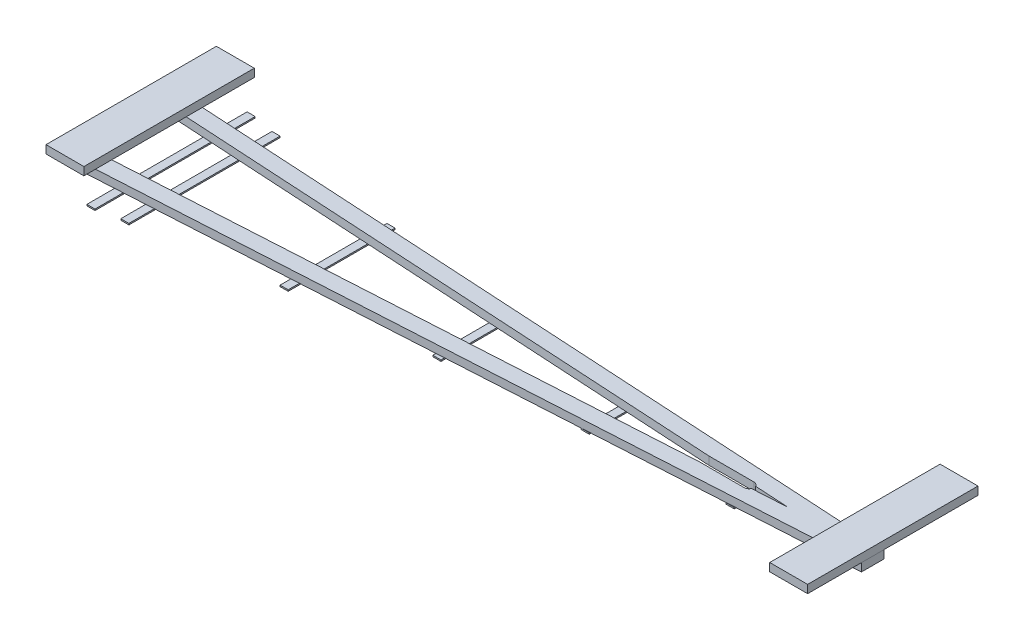
SolidWorks part; units mm, degrees
ref_plane "Front Plane" through (0, 0, 0) normal (0, 0, 1) x (1, 0, 0)
ref_plane "Top Plane" through (0, 0, 0) normal (0, 1, 0) x (1, 0, 0)
ref_plane "Right Plane" through (0, 0, 0) normal (1, 0, 0) x (0, 0, -1)
sketch "Sketch2" plane through (0, 0, 0) normal (0, 1, 0) x (1, 0, 0)
  line L0 (23, 0) -> (23, 355.0006)
  line L1 (23, 355.0006) -> (42.05, 355.0006)
  line L2 (42.05, 355.0006) -> (42.05, 0)
  line L3 (42.05, 0) -> (23, 0)
  line L4 (42.05, 177.5003) -> (23, 177.5003)
  line L5 (32.525, 177.5003) -> (32.525, 167.5003)
  line L6 (32.525, 177.5003) -> (32.525, 187.5003)
  line L7 (55.525, 177.5003) -> (55.525, 167.5003)
  line L8 (55.525, 177.5003) -> (55.525, 187.5003)
  line L9 (78.525, 177.5003) -> (78.525, 167.5003)
  line L10 (78.525, 177.5003) -> (78.525, 187.5003)
  line L11 (101.525, 177.5003) -> (101.525, 167.5003)
  line L12 (101.525, 177.5003) -> (101.525, 187.5003)
  line L13 (124.525, 177.5003) -> (124.525, 167.5003)
  line L14 (124.525, 177.5003) -> (124.525, 187.5003)
  line L15 (147.525, 177.5003) -> (147.525, 167.5003)
  line L16 (147.525, 177.5003) -> (147.525, 187.5003)
  line L17 (170.525, 177.5003) -> (170.525, 167.5003)
  line L18 (170.525, 177.5003) -> (170.525, 187.5003)
  line L19 (193.525, 177.5003) -> (193.525, 167.5003)
  line L20 (193.525, 177.5003) -> (193.525, 187.5003)
  line L21 (216.525, 177.5003) -> (216.525, 167.5003)
  line L22 (216.525, 177.5003) -> (216.525, 187.5003)
  line L23 (239.525, 177.5003) -> (239.525, 167.5003)
  line L24 (239.525, 177.5003) -> (239.525, 187.5003)
  line L25 (262.525, 177.5003) -> (262.525, 167.5003)
  line L26 (262.525, 177.5003) -> (262.525, 187.5003)
  line L27 (285.525, 177.5003) -> (285.525, 167.5003)
  line L28 (285.525, 177.5003) -> (285.525, 187.5003)
  line L29 (308.525, 177.5003) -> (308.525, 167.5003)
  line L30 (308.525, 177.5003) -> (308.525, 187.5003)
  line L31 (331.525, 177.5003) -> (331.525, 167.5003)
  line L32 (331.525, 177.5003) -> (331.525, 187.5003)
  line L33 (354.525, 177.5003) -> (354.525, 167.5003)
  line L34 (354.525, 177.5003) -> (354.525, 187.5003)
  line L35 (377.525, 177.5003) -> (377.525, 167.5003)
  line L36 (377.525, 177.5003) -> (377.525, 187.5003)
  line L37 (400.525, 177.5003) -> (400.525, 167.5003)
  line L38 (400.525, 177.5003) -> (400.525, 187.5003)
  line L39 (423.525, 177.5003) -> (423.525, 167.5003)
  line L40 (423.525, 177.5003) -> (423.525, 187.5003)
  line L41 (446.525, 177.5003) -> (446.525, 167.5003)
  line L42 (446.525, 177.5003) -> (446.525, 187.5003)
  line L43 (469.525, 177.5003) -> (469.525, 167.5003)
  line L44 (469.525, 177.5003) -> (469.525, 187.5003)
  line L45 (492.525, 177.5003) -> (492.525, 167.5003)
  line L46 (492.525, 177.5003) -> (492.525, 187.5003)
  line L47 (515.525, 177.5003) -> (515.525, 167.5003)
  line L48 (515.525, 177.5003) -> (515.525, 187.5003)
  line L49 (538.525, 177.5003) -> (538.525, 167.5003)
  line L50 (538.525, 177.5003) -> (538.525, 187.5003)
  line L51 (561.525, 177.5003) -> (561.525, 167.5003)
  line L52 (561.525, 177.5003) -> (561.525, 187.5003)
  line L53 (584.525, 177.5003) -> (584.525, 167.5003)
  line L54 (584.525, 177.5003) -> (584.525, 187.5003)
  line L55 (607.525, 177.5003) -> (607.525, 167.5003)
  line L56 (607.525, 177.5003) -> (607.525, 187.5003)
  line L57 (630.525, 177.5003) -> (630.525, 167.5003)
  line L58 (630.525, 177.5003) -> (630.525, 187.5003)
  line L59 (653.525, 177.5003) -> (653.525, 167.5003)
  line L60 (653.525, 177.5003) -> (653.525, 187.5003)
  line L61 (676.525, 177.5003) -> (676.525, 167.5003)
  line L62 (676.525, 177.5003) -> (676.525, 187.5003)
  line L63 (699.525, 177.5003) -> (699.525, 167.5003)
  line L64 (699.525, 177.5003) -> (699.525, 187.5003)
  line L65 (722.525, 177.5003) -> (722.525, 167.5003)
  line L66 (722.525, 177.5003) -> (722.525, 187.5003)
  line L67 (745.525, 177.5003) -> (745.525, 167.5003)
  line L68 (745.525, 177.5003) -> (745.525, 187.5003)
  line L69 (768.525, 177.5003) -> (768.525, 167.5003)
  line L70 (768.525, 177.5003) -> (768.525, 187.5003)
  line L71 (791.525, 177.5003) -> (791.525, 167.5003)
  line L72 (791.525, 177.5003) -> (791.525, 187.5003)
  line L73 (814.525, 177.5003) -> (814.525, 167.5003)
  line L74 (814.525, 177.5003) -> (814.525, 187.5003)
  line L75 (837.525, 177.5003) -> (837.525, 167.5003)
  line L76 (837.525, 177.5003) -> (837.525, 187.5003)
  line L77 (860.525, 177.5003) -> (860.525, 167.5003)
  line L78 (860.525, 177.5003) -> (860.525, 187.5003)
  line L79 (883.525, 177.5003) -> (883.525, 167.5003)
  line L80 (883.525, 177.5003) -> (883.525, 187.5003)
  line L81 (906.525, 177.5003) -> (906.525, 167.5003)
  line L82 (906.525, 177.5003) -> (906.525, 187.5003)
  line L83 (929.525, 177.5003) -> (929.525, 167.5003)
  line L84 (929.525, 177.5003) -> (929.525, 187.5003)
  line L85 (952.525, 177.5003) -> (952.525, 167.5003)
  line L86 (952.525, 177.5003) -> (952.525, 187.5003)
  line L87 (975.525, 177.5003) -> (975.525, 167.5003)
  line L88 (975.525, 177.5003) -> (975.525, 187.5003)
  line L89 (998.525, 177.5003) -> (998.525, 167.5003)
  line L90 (998.525, 177.5003) -> (998.525, 187.5003)
  line L91 (1021.525, 177.5003) -> (1021.525, 167.5003)
  line L92 (1021.525, 177.5003) -> (1021.525, 187.5003)
  line L93 (1044.525, 177.5003) -> (1044.525, 167.5003)
  line L94 (1044.525, 177.5003) -> (1044.525, 187.5003)
  line L95 (1067.525, 177.5003) -> (1067.525, 167.5003)
  line L96 (1067.525, 177.5003) -> (1067.525, 187.5003)
  line L97 (1090.525, 177.5003) -> (1090.525, 167.5003)
  line L98 (1090.525, 177.5003) -> (1090.525, 187.5003)
  line L99 (1113.525, 177.5003) -> (1113.525, 167.5003)
  line L100 (1113.525, 177.5003) -> (1113.525, 187.5003)
  line L101 (1136.525, 177.5003) -> (1136.525, 167.5003)
  line L102 (1136.525, 177.5003) -> (1136.525, 187.5003)
  line L103 (-3.95, 177.5003) -> (-23, 177.5003)
  line L104 (-13.475, 177.5003) -> (-13.475, 187.5003)
  line L105 (65.05, 177.5003) -> (46, 177.5003)
  line L106 (88.05, 177.5003) -> (69, 177.5003)
  line L107 (111.05, 177.5003) -> (92, 177.5003)
  line L108 (134.05, 177.5003) -> (115, 177.5003)
  line L109 (157.05, 177.5003) -> (138, 177.5003)
  line L110 (180.05, 177.5003) -> (161, 177.5003)
  line L111 (203.05, 177.5003) -> (184, 177.5003)
  line L112 (226.05, 177.5003) -> (207, 177.5003)
  line L113 (249.05, 177.5003) -> (230, 177.5003)
  line L114 (272.05, 177.5003) -> (253, 177.5003)
  line L115 (295.05, 177.5003) -> (276, 177.5003)
  line L116 (318.05, 177.5003) -> (299, 177.5003)
  line L117 (341.05, 177.5003) -> (322, 177.5003)
  line L118 (364.05, 177.5003) -> (345, 177.5003)
  line L119 (387.05, 177.5003) -> (368, 177.5003)
  line L120 (410.05, 177.5003) -> (391, 177.5003)
  line L121 (433.05, 177.5003) -> (414, 177.5003)
  line L122 (456.05, 177.5003) -> (437, 177.5003)
  line L123 (479.05, 177.5003) -> (460, 177.5003)
  line L124 (502.05, 177.5003) -> (483, 177.5003)
  line L125 (525.05, 177.5003) -> (506, 177.5003)
  line L126 (548.05, 177.5003) -> (529, 177.5003)
  line L127 (571.05, 177.5003) -> (552, 177.5003)
  line L128 (594.05, 177.5003) -> (575, 177.5003)
  line L129 (617.05, 177.5003) -> (598, 177.5003)
  line L130 (640.05, 177.5003) -> (621, 177.5003)
  line L131 (663.05, 177.5003) -> (644, 177.5003)
  line L132 (686.05, 177.5003) -> (667, 177.5003)
  line L133 (709.05, 177.5003) -> (690, 177.5003)
  line L134 (732.05, 177.5003) -> (713, 177.5003)
  line L135 (755.05, 177.5003) -> (736, 177.5003)
  line L136 (778.05, 177.5003) -> (759, 177.5003)
  line L137 (801.05, 177.5003) -> (782, 177.5003)
  line L138 (824.05, 177.5003) -> (805, 177.5003)
  line L139 (847.05, 177.5003) -> (828, 177.5003)
  line L140 (870.05, 177.5003) -> (851, 177.5003)
  line L141 (893.05, 177.5003) -> (874, 177.5003)
  line L142 (916.05, 177.5003) -> (897, 177.5003)
  line L143 (939.05, 177.5003) -> (920, 177.5003)
  line L144 (962.05, 177.5003) -> (943, 177.5003)
  line L145 (985.05, 177.5003) -> (966, 177.5003)
  line L146 (1008.05, 177.5003) -> (989, 177.5003)
  line L147 (1031.05, 177.5003) -> (1012, 177.5003)
  line L148 (1054.05, 177.5003) -> (1035, 177.5003)
  line L149 (1077.05, 177.5003) -> (1058, 177.5003)
  line L150 (1100.05, 177.5003) -> (1081, 177.5003)
  line L151 (1123.05, 177.5003) -> (1104, 177.5003)
  line L152 (1146.05, 177.5003) -> (1127, 177.5003)
  line L153 (-13.475, 177.5003) -> (-13.475, 167.5003)
  line L154 (345, 177.5003) -> (345, 303.0106)
  line L155 (345, 303.0106) -> (364.05, 303.0106)
  line L156 (364.05, 303.0106) -> (364.05, 51.99)
  line L157 (364.05, 51.99) -> (345, 51.99)
  line L158 (345, 51.99) -> (345, 177.5003)
  line L159 (667, 177.5003) -> (667, 266.2276)
  line L160 (667, 266.2276) -> (686.05, 266.2276)
  line L161 (686.05, 266.2276) -> (686.05, 88.773)
  line L162 (686.05, 88.773) -> (667, 88.773)
  line L163 (667, 88.773) -> (667, 177.5003)
  line L164 (989, 177.5003) -> (989, 240.2243)
  line L165 (989, 240.2243) -> (1008.05, 240.2243)
  line L166 (1008.05, 240.2243) -> (1008.05, 114.7763)
  line L167 (1008.05, 114.7763) -> (989, 114.7763)
  line L168 (989, 114.7763) -> (989, 177.5003)
  line L169 (1311, 177.5003) -> (1311, 221.8207)
  line L170 (1311, 221.8207) -> (1330.05, 221.8207)
  line L171 (1330.05, 221.8207) -> (1330.05, 133.1798)
  line L172 (1330.05, 133.1798) -> (1311, 133.1798)
  line L173 (1311, 133.1798) -> (1311, 177.5003)
  line L174 (-26.95, 177.5003) -> (-46, 177.5003)
  line L175 (1159.525, 177.5003) -> (1159.525, 167.5003) [skipped]
  line L176 (1159.525, 177.5003) -> (1159.525, 187.5003) [skipped]
  line L177 (1169.05, 177.5003) -> (1150, 177.5003) [skipped]
  line L178 (-36.475, 177.5003) -> (-36.475, 187.5003)
  line L179 (-36.475, 177.5003) -> (-36.475, 167.5003)
  line L180 (-26.95, 177.5003) -> (-26.95, 365.5543)
  line L181 (-26.95, 365.5543) -> (-46, 365.5543)
  line L182 (-46, 365.5543) -> (-46, -10.5537)
  line L183 (-46, -10.5537) -> (-26.95, -10.5537)
  line L184 (-26.95, -10.5537) -> (-26.95, 177.5003)
  line L185 (-36.475, 177.5003) -> (-36.475, 74.0706)
  line L186 (32.525, 177.5003) -> (32.525, 79.8751)
  line L187 (308.525, 177.5003) -> (308.525, 108.4802)
  line L188 (584.525, 177.5003) -> (584.525, 128.7085)
  line L189 (860.525, 177.5003) -> (860.525, 143.0084)
  line L190 (1136.525, 177.5003) -> (1136.525, 153.1172)
  line L191 (1169.05, 177.5003) -> (1150, 177.5003)
  line L192 (1159.525, 177.5003) -> (1159.525, 187.5003)
  line L193 (1159.525, 177.5003) -> (1159.525, 167.5003)
  line L194 (1192.05, 177.5003) -> (1173, 177.5003)
  line L195 (1182.525, 177.5003) -> (1182.525, 187.5003)
  line L196 (1182.525, 177.5003) -> (1182.525, 167.5003)
  line L197 (1215.05, 177.5003) -> (1196, 177.5003)
  line L198 (1205.525, 177.5003) -> (1205.525, 187.5003)
  line L199 (1205.525, 177.5003) -> (1205.525, 167.5003)
  line L200 (1238.05, 177.5003) -> (1219, 177.5003)
  line L201 (1228.525, 177.5003) -> (1228.525, 187.5003)
  line L202 (1228.525, 177.5003) -> (1228.525, 167.5003)
  line L203 (1261.05, 177.5003) -> (1242, 177.5003)
  line L204 (1251.525, 177.5003) -> (1251.525, 187.5003)
  line L205 (1251.525, 177.5003) -> (1251.525, 167.5003)
  line L206 (1284.05, 177.5003) -> (1265, 177.5003)
  line L207 (1274.525, 177.5003) -> (1274.525, 187.5003)
  line L208 (1274.525, 177.5003) -> (1274.525, 167.5003)
  line L209 (1307.05, 177.5003) -> (1288, 177.5003)
  line L210 (1297.525, 177.5003) -> (1297.525, 187.5003)
  line L211 (1297.525, 177.5003) -> (1297.525, 167.5003)
  line L212 (1330.05, 177.5003) -> (1311, 177.5003)
  line L213 (1320.525, 177.5003) -> (1320.525, 187.5003)
  line L214 (1320.525, 177.5003) -> (1320.525, 167.5003)
  circle A0 centre (-36.475, 74.0706) radius 2
  circle A1 centre (-36.475, 280.93) radius 2
  circle A2 centre (32.525, 79.8751) radius 2
  circle A3 centre (32.525, 275.1254) radius 2
  circle A4 centre (354.525, 108.4802) radius 2
  circle A5 centre (354.525, 246.5203) radius 2
  circle A6 centre (676.525, 128.7085) radius 2
  circle A7 centre (676.525, 226.292) radius 2
  circle A8 centre (998.525, 143.0084) radius 2
  circle A9 centre (998.525, 211.9922) radius 2
  circle A10 centre (1320.525, 153.1172) radius 2
  circle A11 centre (1320.525, 201.8834) radius 2
  dimension "D5" = 9
  dimension "D1" = 50
  dimension "D3" = 2
  dimension "D2" = 50
  dimension "D4" = 2
extrude "Boss-Extrude1" add sketch "Sketch2" along normal blind 3.175 contours A0 L174 L182 L183 L184 | L181 L182 L174 L180 A1 | L4 L2 L1 L0 A3 | A2 L4 L0 L3 L2 | A4 L116 L158 L157 L156 | L156 L155 L154 L116 A5 | A6 L128 L163 L162 L161 | L161 L160 L159 L128 A7 | L166 L165 L164 L140 A9 | A8 L140 L168 L167 L166 | L171 L170 L169 L152 A11 | A10 L152 L173 L172 L171 region at (24.7852, 0, -88.7501) region at (32.525, 0, -266.2173) region at (354.525, 0, -114.7782) region at (354.525, 0, -240.2223) region at (676.525, 0, -133.1698) region at (676.525, 0, -221.8308) region at (998.525, 0, -146.1715) region at (998.525, 0, -208.829) region at (1320.525, 0, -155.3736) region at (1320.525, 0, -199.6269) region at (-28.8402, 0, -83.4733) region at (-36.475, 0, -271.4942)
sketch "Sketch3" plane through (0, 3.175, 0) normal (0, 1, 0) x (1, 0, 0)
  line L0 (1330.05, 177.5003) -> (1330.05, 190.2003)
  line L1 (-46, 177.5003) -> (1330.05, 177.5003)
  line L2 (-46, 365.5543) -> (-46, -10.5537) construction
  line L3 (1330.05, 221.8207) -> (1330.05, 133.1798) construction
  line L4 (1330.05, 190.2003) -> (-46, 190.2003)
  line L7 (1330.05, 164.8003) -> (1330.05, 177.5003)
  line L8 (1330.05, 190.2003) -> (1330.05, 330.2003)
  line L9 (1330.05, 330.2003) -> (-46, 330.2003)
  line L10 (-46, 330.2003) -> (-46, 190.2003)
  line L14 (-36.475, 365.5543) -> (-177.385, 365.5543)
  line L15 (-26.95, 365.5543) -> (-46, 365.5543) construction
  line L16 (-46, 330.2003) -> (-177.385, 330.2003)
  line L17 (-177.385, 330.2003) -> (-177.385, 190.2003)
  line L18 (-177.385, 190.2003) -> (-46, 190.2003)
  line L19 (1330.05, 24.8003) -> (1610.805, 24.8003)
  line L20 (1610.805, 24.8003) -> (1610.805, 164.8003)
  line L21 (1610.805, 164.8003) -> (1330.05, 164.8003)
  line L22 (1320.525, 221.8207) -> (1610.805, 221.8207)
  line L23 (1311, 221.8207) -> (1330.05, 221.8207) construction
  line L24 (1330.05, 330.2003) -> (1610.805, 330.2003)
  line L25 (1610.805, 330.2003) -> (1610.805, 190.2003)
  line L26 (1610.805, 190.2003) -> (1330.05, 190.2003)
  line L30 (1330.05, 164.8003) -> (-46, 164.8003)
  line L31 (-177.385, 164.8003) -> (-46, 164.8003)
  line L32 (-177.385, 24.8003) -> (-177.385, 164.8003)
  line L33 (1330.05, 24.8003) -> (-46, 24.8003)
  line L34 (-46, 24.8003) -> (-177.385, 24.8003)
  line M2 (-26.95, -10.5537) -> (-26.95, 365.5543)
  line M4 (-46, 365.5543) -> (-46, -10.5537)
  circle M6 centre (-36.475, 280.93) radius 2
extrude "Boss-Extrude2" add sketch "Sketch3" along normal blind 19 separate body contours L8 L9 L4 M2 | L17 L18 L16 M4 | L25 L24 L8 L22 | L26 L25 L22 L8 | L9 L4 M2 M4 M6 | M6 | L30 L31 L32 L34 L33 L19 L20 L21 region at (651.55, 3.175, -260.2003) region at (1470.4275, 3.175, -206.0105) region at (-36.475, 3.175, -260.1021) region at (1470.4275, 3.175, -276.0105) region at (-111.6925, 3.175, -260.2003) region at (-36.475, 3.175, -280.93)
sketch "Sketch4" plane through (0, 3.175, 0) normal (0, -1, 0) x (1, 0, 0)
  line L0 (-36.475, -280.93) -> (1320.525, -201.8834)
  line L1 (-37.5799, -261.9621) -> (1319.4201, -182.9155)
  line L2 (-35.3701, -299.8978) -> (1321.6299, -220.8512)
  line L3 (-37.5799, -261.9621) -> (-177.385, -270.1059)
  line L4 (-177.385, -330.2003) -> (-177.385, -190.2003) construction
  line L5 (-35.3701, -299.8978) -> (-177.385, -308.1703)
  line L6 (-177.385, -308.1703) -> (-177.385, -270.1059)
  line L7 (1319.4201, -182.9155) -> (1610.805, -165.942)
  line L8 (1321.6299, -220.8512) -> (1610.805, -204.0065)
  line L9 (1610.805, -330.2003) -> (1610.805, -190.2003) construction
  line L10 (1610.805, -204.0065) -> (1610.805, -165.942)
  line L11 (-177.385, -164.8003) -> (-177.385, -190.2003)
  line L12 (-177.385, -190.2003) -> (-177.385, -177.5003)
  line L13 (-177.385, -177.5003) -> (345.7065, -177.5003)
  line L14 (1321.6299, -134.1494) -> (1610.805, -150.9941)
  line L15 (-35.3701, -55.1027) -> (1321.6299, -134.1494)
  line L16 (-35.3701, -55.1027) -> (-177.385, -46.8302)
  line L17 (-177.385, -46.8302) -> (-177.385, -84.8946)
  line L18 (-37.5799, -93.0384) -> (-177.385, -84.8946)
  line L19 (-37.5799, -93.0384) -> (1319.4201, -172.0851)
  line L20 (1319.4201, -172.0851) -> (1412.3837, -177.5003)
  line L21 (1610.805, -150.9941) -> (1610.805, -189.0585)
  line L26 (1610.805, -330.2003) -> (1610.805, -190.2003)
  line L27 (1610.805, -330.2003) -> (1610.805, -190.2003)
  line L28 (1610.805, -190.2003) -> (-177.385, -190.2003)
  line L29 (1610.805, -190.2003) -> (-177.385, -190.2003)
  line L30 (-177.385, -190.2003) -> (-177.385, -330.2003)
  line L31 (-177.385, -190.2003) -> (-177.385, -330.2003)
  line L32 (-177.385, -330.2003) -> (1610.805, -330.2003)
  line L33 (-177.385, -330.2003) -> (1610.805, -330.2003)
  circle A0 centre (1320.525, -201.8834) radius 2 construction
  circle A3 centre (998.525, -211.9922) radius 2 construction
  circle A4 centre (354.525, -246.5203) radius 2 construction
  circle A5 centre (32.525, -275.1254) radius 2 construction
  circle A6 centre (-36.475, -280.93) radius 2 construction
  circle A7 centre (1320.525, -201.8834) radius 2
  circle A8 centre (998.525, -211.9922) radius 2
  circle A9 centre (354.525, -246.5203) radius 2
  circle A10 centre (32.525, -275.1254) radius 2
  circle A11 centre (-36.475, -280.93) radius 2
  line M13 (1610.805, -190.2003) -> (-177.385, -190.2003)
  line M20 (1610.805, -330.2003) -> (1610.805, -190.2003)
  line M40 (-177.385, -190.2003) -> (-177.385, -330.2003)
  dimension "D2" = 19
  dimension "D1" = 0
  dimension "D3" = 19
extrude "Boss-Extrude3" add sketch "Sketch4" against normal blind 19 separate body contours L21 L14 L15 L16 L17 L18 L19 L20 L7 | L2 L8 L1 L3 L5 A11 A10 A7 A9 A8 M20 M13 M40 | L10 L7 L1 M13 region at (656.2913, 3.175, -241.4583) region at (1471.9906, 3.175, -182.1142) region at (687.8405, 3.175, -115.8678)
sketch "Sketch5" plane through (0, 22.175, 0) normal (0, 1, 0) x (1, 0, 0)
  line L0 (1610.805, 24.8003) -> (1610.805, 164.8003) construction
  line L1 (1610.805, 330.2003) -> (1610.805, 190.2003) construction
  line L2 (-177.385, 24.8003) -> (-177.385, 164.8003) construction
  line L3 (-177.385, 330.2003) -> (-177.385, 190.2003) construction
  line L4 (1610.805, 24.8003) -> (1610.805, 164.8003)
  line L5 (1610.805, 330.2003) -> (1610.805, 190.2003)
  line L6 (-177.385, 24.8003) -> (-177.385, 164.8003)
  line L7 (-177.385, 330.2003) -> (-177.385, 190.2003)
  line L8 (-177.385, 24.8003) -> (-88.385, 24.8003)
  line L9 (1610.805, 24.8003) -> (-177.385, 24.8003) construction
  line L10 (-88.385, 24.8003) -> (-88.385, 424.8003)
  line L11 (-88.385, 424.8003) -> (-177.385, 424.8003)
  line L12 (-177.385, 424.8003) -> (-177.385, 24.8003)
  line L13 (1610.805, 24.8003) -> (1610.805, 424.8003)
  line L14 (1610.805, 424.8003) -> (1521.805, 424.8003)
  line L15 (1521.805, 424.8003) -> (1521.805, 24.8003)
  line L16 (1521.805, 24.8003) -> (1610.805, 24.8003)
  line M1 (1610.805, 150.9941) -> (1610.805, 204.0065)
  line M2 (1610.805, 204.0065) -> (-177.385, 308.1703)
  line M3 (-177.385, 308.1703) -> (-177.385, 270.1059)
  line M4 (-177.385, 270.1059) -> (1412.3837, 177.5003)
  line M5 (1412.3837, 177.5003) -> (-177.385, 84.8946)
  line M6 (-177.385, 84.8946) -> (-177.385, 46.8302)
  line M7 (-177.385, 46.8302) -> (1610.805, 150.9941)
extrude "Boss-Extrude4" add sketch "Sketch5" along normal blind 19 separate body contours L14 L15 L5 L13 M2 | L15 L16 L4 M7 | L15 M2 M7 M1 | L11 L12 L7 L10 M2 | L10 M4 M2 M3 | L7 L12 L6 L10 M5 M4 | L10 M7 M5 M6 | L8 L10 L11 L12 region at (1566.6161, 22.175, -86.6102) region at (1564.9836, 22.175, -177.5003) region at (1566.4812, 22.175, -315.6943) region at (-132.885, 22.175, -68.4546) region at (-132.5625, 22.175, -365.1798) region at (-132.885, 22.175, -286.5459) region at (-133.3122, 22.175, -177.5003)
delete or keep bodies "Body-Delete/Keep 1" type delete bodies bodies 109 108
sketch "Sketch6" plane through (0, 22.175, 0) normal (0, 1, 0) x (1, 0, 0)
  circle A0 centre (-36.475, 280.93) radius 2 construction
  circle A1 centre (354.525, 246.5203) radius 2 construction
  circle A2 centre (998.525, 211.9922) radius 2 construction
  circle A3 centre (1320.525, 201.8834) radius 2 construction
  circle A4 centre (-36.475, 280.93) radius 2
  circle A5 centre (354.525, 246.5203) radius 2
  circle A6 centre (998.525, 211.9922) radius 2
  circle A7 centre (1320.525, 201.8834) radius 2
  point P12 (0, 0)
  circle M8 centre (32.525, 275.1254) radius 2
  circle M10 centre (-36.475, 280.93) radius 2
  circle M11 centre (354.525, 246.5203) radius 2
  circle M12 centre (998.525, 211.9922) radius 2
extrude "Boss-Extrude5" add sketch "Sketch6" against normal blind 19 contours M10 | M8 | M11 | M12 | A7 region at (-36.475, 22.175, -280.93) region at (354.525, 22.175, -246.5203) region at (998.525, 22.175, -211.9922) region at (32.525, 22.175, -275.1254)
sketch "Sketch7" plane through (0, 22.175, 0) normal (0, 1, 0) x (1, 0, 0)
  line L0 (1311, 221.8207) -> (1330.05, 221.8207) construction
  line L1 (1330.05, 133.1798) -> (1311, 133.1798) construction
  line L2 (1311, 221.8207) -> (1330.05, 221.8207)
  line L3 (1330.05, 133.1798) -> (1311, 133.1798)
  line L4 (1320.525, 133.1798) -> (1320.525, 221.8207)
  line L5 (1320.525, 166.0003) -> (1214.9622, 166.0003)
  line L6 (1320.525, 189.0003) -> (1214.9622, 189.0003)
  line L7 (-177.385, 270.1059) -> (1412.3837, 177.5003) construction
  line L8 (1412.3837, 177.5003) -> (-177.385, 84.8946) construction
  line L9 (-177.385, 270.1059) -> (1412.3837, 177.5003)
  line L10 (1412.3837, 177.5003) -> (-177.385, 84.8946)
  circle A0 centre (1320.525, 177.5003) radius 11.5
  line M5 (-177.385, 270.1059) -> (1412.3837, 177.5003)
  line M6 (1412.3837, 177.5003) -> (-177.385, 84.8946)
extrude "Cut-Extrude1" cut sketch "Sketch7" against normal blind 19 contours A0 L4 M6 | A0 L10 L5 | L4 A0 L10 | A0 L4 M5 | L4 A0 L9 | A0 L6 M5 region at (1316.7097, 22.175, -169.4592) region at (1280.7113, 22.175, -167.8422) region at (1324.7159, 22.175, -169.8007) region at (1316.7097, 22.175, -185.5413) region at (1324.7159, 22.175, -185.1999) region at (1280.7113, 22.175, -187.1584)
